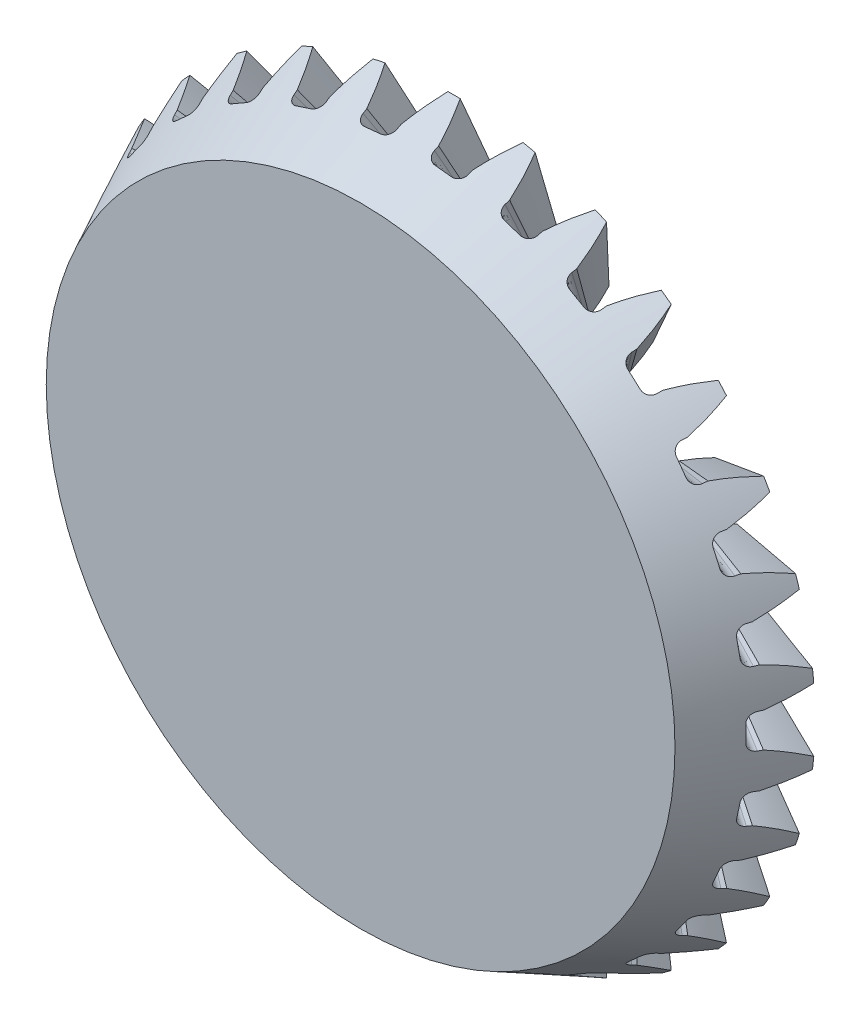
SolidWorks part; units mm, degrees
ref_plane "Front Plane" through (0, 0, 0) normal (0, 0, 1) x (1, 0, 0)
ref_plane "Top Plane" through (0, 0, 0) normal (0, 1, 0) x (1, 0, 0)
ref_plane "Right Plane" through (0, 0, 0) normal (1, 0, 0) x (0, 0, -1)
ref_axis "Gear Axis" through (0, 0, -1.8867) along (0, 0, 1)
sketch "Blank Sketch" plane through (0, 0, 0) normal (0, 1, 0) x (1, 0, 0)
  line L0 (0, 0) -> (0, -37.7336) construction
  line L1 (0, 0) -> (33.75, -16.875) construction
  line L2 (0, 0) -> (23.0169, -11.5084) construction
  line L3 (19.7149, -18.1124) -> (23.4062, -10.7298)
  line L4 (23.4062, -10.7298) -> (34.4091, -15.5568)
  line L5 (34.4091, -15.5568) -> (29.9574, -24.4601)
  line L6 (29.9574, -24.4601) -> (0, -24.4601)
  line L7 (0, -24.4601) -> (0, -18.1124)
  line L8 (0, -18.1124) -> (19.7149, -18.1124)
  line L9 (33.75, -16.875) -> (34.4091, -15.5568) construction
  line L10 (33.75, -16.875) -> (29.9574, -24.4601) construction
  line L11 (23.0169, -11.5084) -> (19.7149, -18.1124) construction
  dimension "Axis" = 37.7336
  dimension "Cone" = 63.435
  dimension "Heel" = 37.7336
  dimension "Toe Cone" = 63.435
  dimension "Toe" = 25.7336
  dimension "Heel Square" = 90
  dimension "Addendum" = 1.4737
  dimension "Root Square" = 90
  dimension "Heel Rim" = 8.4804
  dimension "Toe Square" = 90
  dimension "Toe Rim" = 7.3835
  dimension "Front Square" = 90
  dimension "Face" = 2.878
  dimension "Back" = 29.9574
  dimension "Front" = 19.7149
revolve "Blank" add sketch "Blank Sketch" angle 360 about L0
sketch "Cone Sketch" plane through (0, 0, 0) normal (0, 1, 0) x (1, 0, 0)
  line L0 (0, 0) -> (0, -37.7336) construction
  line L1 (0, 0) -> (35.7625, -17.8812)
  line L2 (0, 0) -> (21.0044, -10.5022)
  dimension "Axis" = 37.7336
  dimension "Toe Cone" = 63.435
  dimension "Heel Cone" = 63.435
  dimension "Heel" = 39.9836
  dimension "Toe" = 23.4836
ref_plane "Heel Plane" through (35.7625, 0, 17.8812) normal (0.8944, 0, 0.4472) x (0.4472, 0, -0.8944)
ref_plane "Toe Plane" through (21.0044, 0, 10.5022) normal (0.8944, 0, 0.4472) x (0.4472, 0, -0.8944)
sketch "Heel Section Sketch" plane through (35.7625, 0, 17.8812) normal (0.8944, 0, 0.4472) x (0.4472, 0, -0.8944)
  line L0 (0, 0) -> (-79.9673, 0) construction
  line L1 (-2.3155, 1.7439) -> (-2.7737, 1.7336)
  line L2 (-2.3155, -1.7439) -> (-2.7737, -1.7336)
  line L3 (3.8303, 4.4017) -> (3.8303, -4.4017)
  arc A0 (-2.7737, 1.7336) -> (-3.6593, 0.8182) centre (-2.7534, 0.8279) ccw
  arc A1 (-3.6593, -0.8182) -> (-2.7737, -1.7336) centre (-2.7534, -0.8279) ccw
  arc A2 (-3.6593, -0.8182) -> (-3.6593, 0.8182) centre (-79.9673, 0) ccw
  spline S0 degree 4 poles (-2.744, 1.6269) (-2.7139, 1.6348) (-2.656, 1.6501) (-2.5703, 1.6726) (-2.3625, 1.7303) (-2.2536, 1.7614) (-1.9817, 1.8415) (-1.815, 1.8938) (-1.5868, 1.966) (-1.3967, 2.0294) (-1.1845, 2.1011) (-0.9868, 2.1708) (-0.7813, 2.2447) (-0.5817, 2.3187) (-0.3792, 2.3956) (-0.1799, 2.4731) (0.0312, 2.5573) (0.2888, 2.6623) (0.599, 2.7931) (0.9495, 2.9454) (1.3482, 3.1267) (1.727, 3.3036) (2.1308, 3.5012) (2.4875, 3.6786) (2.9149, 3.9021) (3.2191, 4.0621) (3.6932, 4.3242) (3.8787, 4.4285) (4.163, 4.5912) (4.3066, 4.6749) (4.3738, 4.7143) (4.4114, 4.7364) knots 0 0 0 0 0 0.014246 0.028492 0.056481 0.083968 0.111456 0.138944 0.166431 0.193919 0.221407 0.248895 0.276382 0.30387 0.331358 0.358846 0.386333 0.419446 0.474422 0.529397 0.584373 0.639348 0.694324 0.749299 0.804274 0.85925 0.914226 0.957113 0.978556 1 1 1 1 1 construction
  spline S1 degree 4 poles (-2.3155, 1.7439) (-2.2712, 1.7566) (-2.1847, 1.7817) (-1.9817, 1.8415) (-1.815, 1.8938) (-1.5868, 1.966) (-1.3967, 2.0294) (-1.1845, 2.1011) (-0.9868, 2.1708) (-0.7813, 2.2447) (-0.5817, 2.3187) (-0.3792, 2.3956) (-0.1799, 2.4731) (0.0312, 2.5573) (0.2888, 2.6623) (0.599, 2.7931) (0.9495, 2.9454) (1.3482, 3.1267) (1.727, 3.3036) (2.1308, 3.5012) (2.4875, 3.6786) (2.9149, 3.9021) (3.2191, 4.0621) (3.5954, 4.2701) (3.7499, 4.3563) (3.8303, 4.4017) knots 0.056481 0.056481 0.056481 0.056481 0.056481 0.083968 0.111456 0.138944 0.166431 0.193919 0.221407 0.248895 0.276382 0.30387 0.331358 0.358846 0.386333 0.419446 0.474422 0.529397 0.584373 0.639348 0.694324 0.749299 0.804274 0.85925 0.914226 0.914226 0.914226 0.914226 0.914226
  spline S2 degree 4 poles (-2.744, -1.6269) (-2.7139, -1.6348) (-2.656, -1.6501) (-2.5703, -1.6726) (-2.3625, -1.7303) (-2.2536, -1.7614) (-1.9817, -1.8415) (-1.815, -1.8938) (-1.5868, -1.966) (-1.3967, -2.0294) (-1.1845, -2.1011) (-0.9868, -2.1708) (-0.7813, -2.2447) (-0.5817, -2.3187) (-0.3792, -2.3956) (-0.1799, -2.4731) (0.0312, -2.5573) (0.2888, -2.6623) (0.599, -2.7931) (0.9495, -2.9454) (1.3482, -3.1267) (1.727, -3.3036) (2.1308, -3.5012) (2.4875, -3.6786) (2.9149, -3.9021) (3.2191, -4.0621) (3.6932, -4.3242) (3.8787, -4.4285) (4.163, -4.5912) (4.3066, -4.6749) (4.3738, -4.7143) (4.4114, -4.7364) knots 0 0 0 0 0 0.014246 0.028492 0.056481 0.083968 0.111456 0.138944 0.166431 0.193919 0.221407 0.248895 0.276382 0.30387 0.331358 0.358846 0.386333 0.419446 0.474422 0.529397 0.584373 0.639348 0.694324 0.749299 0.804274 0.85925 0.914226 0.957113 0.978556 1 1 1 1 1 construction
  spline S3 degree 4 poles (-2.3155, -1.7439) (-2.2712, -1.7566) (-2.1847, -1.7817) (-1.9817, -1.8415) (-1.815, -1.8938) (-1.5868, -1.966) (-1.3967, -2.0294) (-1.1845, -2.1011) (-0.9868, -2.1708) (-0.7813, -2.2447) (-0.5817, -2.3187) (-0.3792, -2.3956) (-0.1799, -2.4731) (0.0312, -2.5573) (0.2888, -2.6623) (0.599, -2.7931) (0.9495, -2.9454) (1.3482, -3.1267) (1.727, -3.3036) (2.1308, -3.5012) (2.4875, -3.6786) (2.9149, -3.9021) (3.2191, -4.0621) (3.5954, -4.2701) (3.7499, -4.3563) (3.8303, -4.4017) knots 0.056481 0.056481 0.056481 0.056481 0.056481 0.083968 0.111456 0.138944 0.166431 0.193919 0.221407 0.248895 0.276382 0.30387 0.331358 0.358846 0.386333 0.419446 0.474422 0.529397 0.584373 0.639348 0.694324 0.749299 0.804274 0.85925 0.914226 0.914226 0.914226 0.914226 0.914226
  dimension "Root" = 76.3124
  dimension "Fillet" = 0.906
  dimension "Centre" = 79.9673
sketch "Toe Section Sketch" plane through (21.0044, 0, 10.5022) normal (0.8944, 0, 0.4472) x (0.4472, 0, -0.8944)
  line L0 (0, 0) -> (-46.9673, 0) construction
  line L1 (-1.36, 1.0243) -> (-1.6291, 1.0182)
  line L2 (-1.36, -1.0243) -> (-1.6291, -1.0182)
  line L3 (2.2496, 2.5852) -> (2.2496, -2.5852)
  arc A0 (-1.6291, 1.0182) -> (-2.1492, 0.4805) centre (-1.6171, 0.4862) ccw
  arc A1 (-2.1492, -0.4805) -> (-1.6291, -1.0182) centre (-1.6171, -0.4862) ccw
  arc A2 (-2.1492, -0.4805) -> (-2.1492, 0.4805) centre (-46.9673, 0) ccw
  spline S0 degree 4 poles (-1.6116, 0.9555) (-1.594, 0.9602) (-1.56, 0.9691) (-1.5096, 0.9824) (-1.3876, 1.0163) (-1.3236, 1.0345) (-1.1639, 1.0816) (-1.066, 1.1123) (-0.932, 1.1547) (-0.8203, 1.1919) (-0.6957, 1.2341) (-0.5796, 1.275) (-0.4589, 1.3184) (-0.3416, 1.3619) (-0.2227, 1.407) (-0.1057, 1.4526) (0.0183, 1.502) (0.1696, 1.5636) (0.3518, 1.6405) (0.5577, 1.7299) (0.7919, 1.8364) (1.0143, 1.9403) (1.2515, 2.0564) (1.461, 2.1605) (1.7121, 2.2918) (1.8906, 2.3858) (2.1692, 2.5398) (2.2914, 2.6085) (2.4729, 2.7126) (2.5478, 2.7565) (2.5907, 2.7817) knots 0 0 0 0 0 0.014246 0.028492 0.056481 0.083968 0.111456 0.138944 0.166431 0.193919 0.221407 0.248895 0.276382 0.30387 0.331358 0.358846 0.386333 0.419446 0.474422 0.529397 0.584373 0.639348 0.694324 0.749299 0.804274 0.85925 0.914226 0.957113 1 1 1 1 1 construction
  spline S1 degree 4 poles (-1.36, 1.0243) (-1.3339, 1.0317) (-1.2831, 1.0465) (-1.1639, 1.0816) (-1.066, 1.1123) (-0.932, 1.1547) (-0.8203, 1.1919) (-0.6957, 1.2341) (-0.5796, 1.275) (-0.4589, 1.3184) (-0.3416, 1.3619) (-0.2227, 1.407) (-0.1057, 1.4526) (0.0183, 1.502) (0.1696, 1.5636) (0.3518, 1.6405) (0.5577, 1.7299) (0.7919, 1.8364) (1.0143, 1.9403) (1.2515, 2.0564) (1.461, 2.1605) (1.7121, 2.2918) (1.8906, 2.3858) (2.1117, 2.508) (2.2025, 2.5586) (2.2496, 2.5852) knots 0.056481 0.056481 0.056481 0.056481 0.056481 0.083968 0.111456 0.138944 0.166431 0.193919 0.221407 0.248895 0.276382 0.30387 0.331358 0.358846 0.386333 0.419446 0.474422 0.529397 0.584373 0.639348 0.694324 0.749299 0.804274 0.85925 0.914226 0.914226 0.914226 0.914226 0.914226
  spline S2 degree 4 poles (-1.6116, -0.9555) (-1.594, -0.9602) (-1.56, -0.9691) (-1.5096, -0.9824) (-1.3876, -1.0163) (-1.3236, -1.0345) (-1.1639, -1.0816) (-1.066, -1.1123) (-0.932, -1.1547) (-0.8203, -1.1919) (-0.6957, -1.2341) (-0.5796, -1.275) (-0.4589, -1.3184) (-0.3416, -1.3619) (-0.2227, -1.407) (-0.1057, -1.4526) (0.0183, -1.502) (0.1696, -1.5636) (0.3518, -1.6405) (0.5577, -1.7299) (0.7919, -1.8364) (1.0143, -1.9403) (1.2515, -2.0564) (1.461, -2.1605) (1.7121, -2.2918) (1.8906, -2.3858) (2.1692, -2.5398) (2.2914, -2.6085) (2.4729, -2.7126) (2.5478, -2.7565) (2.5907, -2.7817) knots 0 0 0 0 0 0.014246 0.028492 0.056481 0.083968 0.111456 0.138944 0.166431 0.193919 0.221407 0.248895 0.276382 0.30387 0.331358 0.358846 0.386333 0.419446 0.474422 0.529397 0.584373 0.639348 0.694324 0.749299 0.804274 0.85925 0.914226 0.957113 1 1 1 1 1 construction
  spline S3 degree 4 poles (-1.36, -1.0243) (-1.3339, -1.0317) (-1.2831, -1.0465) (-1.1639, -1.0816) (-1.066, -1.1123) (-0.932, -1.1547) (-0.8203, -1.1919) (-0.6957, -1.2341) (-0.5796, -1.275) (-0.4589, -1.3184) (-0.3416, -1.3619) (-0.2227, -1.407) (-0.1057, -1.4526) (0.0183, -1.502) (0.1696, -1.5636) (0.3518, -1.6405) (0.5577, -1.7299) (0.7919, -1.8364) (1.0143, -1.9403) (1.2515, -2.0564) (1.461, -2.1605) (1.7121, -2.2918) (1.8906, -2.3858) (2.1117, -2.508) (2.2025, -2.5586) (2.2496, -2.5852) knots 0.056481 0.056481 0.056481 0.056481 0.056481 0.083968 0.111456 0.138944 0.166431 0.193919 0.221407 0.248895 0.276382 0.30387 0.331358 0.358846 0.386333 0.419446 0.474422 0.529397 0.584373 0.639348 0.694324 0.749299 0.804274 0.85925 0.914226 0.914226 0.914226 0.914226 0.914226
  dimension "Root" = 44.8206
  dimension "Fillet" = 0.5321
  dimension "Centre" = 46.9673
loft "Tooth Space" cut profiles "Heel Section Sketch", "Toe Section Sketch"
pattern_circular "Teeth" count 30 over 360 about axis through (0, 0, -1.8867) along (0, 0, 1) of "Tooth Space"
sketch "Sketch1" plane through (0, 0, 0) normal (0, 1, 0) x (1, 0, 0)
  line L0 (14.1509, 0) -> (-14.1509, 0) construction
  line L3 (0, -12.1912) -> (0, 12.1912) construction
  line L4 (0, 1.8867) -> (0, -39.6203) construction
  point P4 (0, 0)
  point P10 (0, 0)
equation "\"No. of Teeth\"= 30"
equation "\"Module\"= 2.25"
equation "\"Bore Diameter\"= 0"
equation "\"Pressure Angle\"= 20"
equation "\"Shaft Angle\"= 90"
equation "\"Mate Teeth\"= 15"
equation "\"Pitch Cone Angle\"= IIF ( ( \"Mate Teeth\" / \"No. of Teeth\" + cos ( \"Shaft Angle\" ) ) > 0 , atn ( sin ( \"Shaft Angle\" ) / ( \"Mate Teeth\" / \"No. of Teeth\" + cos ( \"Shaft Angle\" ) ) ) , 180 + atn ( sin ( \"Shaft Angle\" ) / ( \"Mate Teeth\" / \"No. of Teeth\" + cos ( \"Shaft Angle\" ) ) ) )"
equation "\"Mate Cone Angle\"= \"Shaft Angle\" - \"Pitch Cone Angle\""
equation "\"Addendum\"= IIF ( \"No. of Teeth\" >= \"Mate Teeth\" , 0.54 * \"Module\" + 0.46 * \"Module\" / ( ( \"No. of Teeth\" * cos ( \"Mate Cone Angle\" ) ) / ( \"Mate Teeth\" * cos ( \"Pitch Cone Angle\" ) ) ) , 2 * \"Module\" - ( 0.54 * \"Module\" + 0.46 * \"Module\" / ( ( \"Mate Teeth\" * cos ( \"Pitch Cone Angle\" ) ) / ( \"No. of Teeth\" * cos ( \"Mate Cone Angle\" ) ) ) ) )"
equation "\"Outer Diameter\"= \"No. of Teeth\" * \"Module\" + 2 * \"Addendum\" * cos ( \"Pitch Cone Angle\" )"
equation "\"Pitch Diameter\"= \"No. of Teeth\" * \"Module\""
equation "\"Backlash\"= 0.3 * \"Module\""
equation "\"Arc Length\"= ( ( \"Module\" * pi ) / 2 + \"Backlash\" - 2 * ( \"Addendum\" - \"Module\" ) * tan ( \"Pressure Angle\" ) )"
equation "\"Fillet Radius\"= 0.38 * \"Module\""
equation "\"Mate Addendum\"= 2 * \"Module\" - \"Addendum\""
equation "\"Dedendum\"= 2.188 * \"Module\" - \"Addendum\""
equation "\"Tooth Depth\"= \"Addendum\" + \"Dedendum\""
equation "\"Mate Dedendum\"= 2.188 * \"Module\" - \"Mate Addendum\""
equation "\"Face Width\"= 12"
equation "\"Cone Distance\"= \"Pitch Diameter\" / ( 2 * sin ( \"Pitch Cone Angle\" ) )"
equation "\"Dedendum Angle\"= atn ( \"Dedendum\" / \"Cone Distance\" )"
equation "\"Mate Dedendum Angle\"= atn ( \"Mate Dedendum\" / \"Cone Distance\" )"
equation "\"Face Angle\"= \"Pitch Cone Angle\" + \"Mate Dedendum Angle\""
equation "\"Root Angle\"= \"Pitch Cone Angle\" - \"Dedendum Angle\""
equation "\"Overrun\"= \"Module\""
equation "\"Back Cone Pitch Diameter\"= \"Pitch Diameter\" / cos ( \"Pitch Cone Angle\" )"
equation "\"Back Cone Outer Diameter\"= \"Back Cone Pitch Diameter\" + 2 * \"Addendum\""
equation "\"Root Diameter\"= \"Back Cone Outer Diameter\" - 2 * \"Tooth Depth\""
equation "\"Base Diameter\"= \"Back Cone Pitch Diameter\" * cos ( \"Pressure Angle\" )"
equation "\"Base Radius\"= \"Base Diameter\" / 2"
equation "\"Tooth Thickness\"= \"Module\" * pi - \"Arc Length\""
equation "\"Half Space Angle\"= ( \"Arc Length\" / \"Back Cone Pitch Diameter\" ) * 180 / pi"
equation "\"Involute Fn\"= tan ( \"Pressure Angle\" ) - \"Pressure Angle\" * pi / 180"
equation "\"Flank Offset\"= \"Arc Length\" / \"Back Cone Pitch Diameter\" - \"Involute Fn\""
equation "\"Tip Cap Diameter\"= \"Back Cone Outer Diameter\" + 2 * \"Module\""
equation "\"Flank Start Diameter\"= IIF ( \"Base Diameter\" >= ( \"Root Diameter\" + 3 * \"Fillet Radius\" ) , \"Base Diameter\" , \"Root Diameter\" + 3 * \"Fillet Radius\" )"
equation "\"Involute t1\"= ( abs ( ( \"Flank Start Diameter\" / \"Base Diameter\" ) ^ 2 - 1 ) ) ^ 0.5"
equation "\"Involute t2\"= ( abs ( ( \"Tip Cap Diameter\" / \"Base Diameter\" ) ^ 2 - 1 ) ) ^ 0.5"
equation "\"Flank Arc Radius\"= ( \"Back Cone Pitch Diameter\" / 2 ) * sin ( \"Pressure Angle\" )"
equation "\"Flank Centre Angle\"= \"Half Space Angle\" + \"Pressure Angle\""
equation "\"Heel Distance\"= \"Cone Distance\" + \"Overrun\""
equation "\"Toe Distance\"= \"Cone Distance\" - \"Face Width\" - \"Overrun\""
equation "\"Heel Scale\"= \"Heel Distance\" / \"Cone Distance\""
equation "\"Toe Scale\"= \"Toe Distance\" / \"Cone Distance\""
equation "\"Heel Virtual Radius\"= \"Heel Distance\" * tan ( \"Pitch Cone Angle\" )"
equation "\"Toe Virtual Radius\"= \"Toe Distance\" * tan ( \"Pitch Cone Angle\" )"
equation "\"Axis@Blank Sketch\"= \"Cone Distance\""
equation "\"Cone@Blank Sketch\"= \"Pitch Cone Angle\""
equation "\"Heel@Blank Sketch\"= \"Cone Distance\""
equation "\"Toe Cone@Blank Sketch\"= \"Pitch Cone Angle\""
equation "\"Toe@Blank Sketch\"= \"Cone Distance\" - \"Face Width\""
equation "\"Addendum@Blank Sketch\"= \"Addendum\""
equation "\"Heel Rim@Blank Sketch\"= \"Dedendum\" + \"Module\" / cos ( \"Pitch Cone Angle\" )"
equation "\"Toe Rim@Blank Sketch\"= \"Dedendum\" - \"Face Width\" * tan ( \"Dedendum Angle\" ) + \"Module\" / cos ( \"Pitch Cone Angle\" )"
equation "\"Face@Blank Sketch\"= \"Mate Dedendum Angle\""
equation "\"Back@Blank Sketch\"= \"Cone Distance\" * sin ( \"Pitch Cone Angle\" ) - \"Dedendum\" * cos ( \"Pitch Cone Angle\" ) - \"Module\" - \"Bore Diameter\" / 2"
equation "\"Front@Blank Sketch\"= ( \"Cone Distance\" - \"Face Width\" ) * sin ( \"Pitch Cone Angle\" ) - ( \"Dedendum\" - \"Face Width\" * tan ( \"Dedendum Angle\" ) + \"Module\" / cos ( \"Pitch Cone Angle\" ) ) * cos ( \"Pitch Cone Angle\" ) - \"Bore Diameter\" / 2"
equation "\"Axis@Cone Sketch\"= \"Cone Distance\""
equation "\"Heel Cone@Cone Sketch\"= \"Pitch Cone Angle\""
equation "\"Heel@Cone Sketch\"= \"Heel Distance\""
equation "\"Toe Cone@Cone Sketch\"= \"Pitch Cone Angle\""
equation "\"Toe@Cone Sketch\"= \"Toe Distance\""
equation "\"Centre@Heel Section Sketch\"= \"Heel Virtual Radius\""
equation "\"Root@Heel Section Sketch\"= ( \"Root Diameter\" / 2 ) * \"Heel Scale\""
equation "\"Fillet@Heel Section Sketch\"= ( \"Fillet Radius\" ) * \"Heel Scale\""
equation "\"Centre@Toe Section Sketch\"= \"Toe Virtual Radius\""
equation "\"Root@Toe Section Sketch\"= ( \"Root Diameter\" / 2 ) * \"Toe Scale\""
equation "\"Fillet@Toe Section Sketch\"= ( \"Fillet Radius\" ) * \"Toe Scale\""
equation "\"Count@Teeth\"= \"No. of Teeth\""
